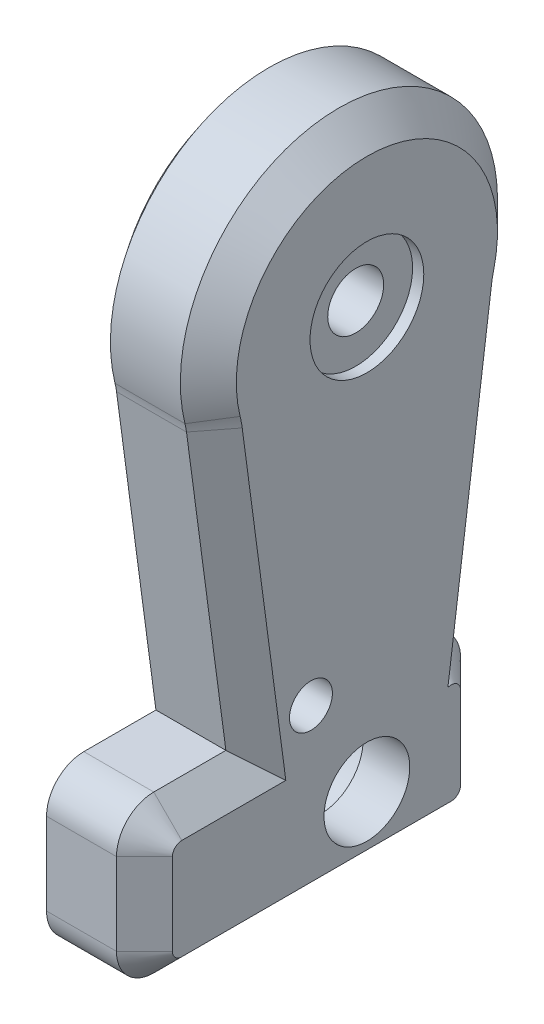
SolidWorks part; units mm, degrees
ref_plane "Front Plane" through (0, 0, 0) normal (0, 0, 1) x (1, 0, 0)
ref_plane "Top Plane" through (0, 0, 0) normal (0, 1, 0) x (1, 0, 0)
ref_plane "Right Plane" through (0, 0, 0) normal (1, 0, 0) x (0, 0, -1)
sketch "Sketch1" plane through (0, 0, 0) normal (1, 0, 0) x (0, 0, -1)
  line L0 (68.3427, -24.9297) -> (63.9535, -57.8487)
  line L1 (65.05, -60.6) -> (65.05, -69.4)
  line L2 (61.05, -73.4) -> (32.15, -73.4)
  line L3 (28.15, -69.4) -> (28.15, -60.6)
  line L4 (32.15, -56.6) -> (39.88, -56.6)
  line L5 (39.88, -56.6) -> (35.6573, -24.9297)
  arc A0 (35.4947, -24.0712) -> (68.5053, -24.0712) centre (52, -20) cw
  arc A1 (68.5053, -24.0712) -> (68.3427, -24.9297) centre (76.2725, -25.987) ccw
  arc A2 (63.9535, -57.8487) -> (65.05, -60.6) centre (61.05, -60.6) cw
  arc A3 (65.05, -69.4) -> (61.05, -73.4) centre (61.05, -69.4) cw
  arc A4 (32.15, -73.4) -> (28.15, -69.4) centre (32.15, -69.4) cw
  arc A5 (28.15, -60.6) -> (32.15, -56.6) centre (32.15, -60.6) cw
  arc A6 (35.6573, -24.9297) -> (35.4947, -24.0712) centre (27.7275, -25.987) ccw
extrude "Boss-Extrude1" add sketch "Sketch1" along normal blind 10.5 from offset 65.9
sketch "Sketch2" plane through (0, 0, 0) normal (1, 0, 0) x (0, 0, -1)
  line L0 (67.5497, -24.824) -> (63.1065, -58.1483)
  line L1 (64.25, -60.6) -> (64.25, -69.4)
  line L2 (61.05, -72.6) -> (32.15, -72.6)
  line L3 (28.95, -69.4) -> (28.95, -60.6)
  line L4 (32.15, -57.4) -> (40.7937, -57.4)
  line L5 (40.7937, -57.4) -> (36.4503, -24.824)
  arc A0 (36.2714, -23.8796) -> (67.7286, -23.8796) centre (52, -20) cw
  arc A1 (67.7286, -23.8796) -> (67.5497, -24.824) centre (76.2725, -25.987) ccw
  arc A2 (63.1065, -58.1483) -> (64.25, -60.6) centre (61.05, -60.6) cw
  arc A3 (64.25, -69.4) -> (61.05, -72.6) centre (61.05, -69.4) cw
  arc A4 (32.15, -72.6) -> (28.95, -69.4) centre (32.15, -69.4) cw
  arc A5 (28.95, -60.6) -> (32.15, -57.4) centre (32.15, -60.6) cw
  arc A6 (36.4503, -24.824) -> (36.2714, -23.8796) centre (27.7275, -25.987) ccw
extrude "Boss-Extrude2" add sketch "Sketch2" along normal blind 0.6 from offset 65.8 separate body
combine bodies "Combine1" operation type subtract main body 101 bodies to subtract 102
chamfer "Chamfer1" distance 3 angle 45 5 edges at (76.4, -41.3892, -66.1481) (76.4, -40.7649, -37.7686) (76.4, -24.4982, -68.4123) (76.4, -24.4982, -35.5877) (76.4, -3, -52)
chamfer "Chamfer2" distance 3 angle 45 8 edges at (76.4, -56.6, -37.5283) (76.4, -57.7716, -29.3216) (76.4, -57.787, -63.8937) (76.4, -65, -28.15) (76.4, -65, -65.05) (76.4, -72.2284, -29.3216) (76.4, -72.2284, -63.8784) (76.4, -73.4, -46.6)
sketch "Sketch3" plane through (0, 0, 0) normal (0, 0, 1) x (1, 0, 0)
  line L1 (65.9, -31.5) -> (68.2, -31.5)
  line L2 (65.9, -31.5) -> (65.9, -8.5)
  line L3 (65.9, -8.5) -> (68.2, -8.5)
  line L4 (68.2, -31.5) -> (68.2, -8.5)
extrude "Boss-Extrude3" add sketch "Sketch3" along normal blind 6.6 from offset 55.3 separate body offset against normal yes
combine bodies "Combine2" operation type subtract main body 103 bodies to subtract 104
sketch "Sketch4" plane through (0, 0, 0) normal (0, 0, 1) x (1, 0, 0)
  line L1 (65.9, -23.3) -> (68.2, -23.3)
  line L2 (65.9, -23.3) -> (65.9, -16.7)
  line L3 (65.9, -16.7) -> (68.2, -16.7)
  line L4 (68.2, -23.3) -> (68.2, -16.7)
extrude "Boss-Extrude4" add sketch "Sketch4" along normal blind 23 from offset 63.5 separate body offset against normal yes
combine bodies "Combine3" operation type subtract main body 105 bodies to subtract 106
sketch "Sketch5" plane through (0, 0, 0) normal (1, 0, 0) x (0, 0, -1)
  circle A0 centre (52, -20) radius 4.6
extrude "Boss-Extrude5" add sketch "Sketch5" along normal blind 2.3 from offset 65.9 separate body
combine bodies "Combine4" operation type subtract main body 107 bodies to subtract 108
sketch "Sketch6" plane through (0, 0, 0) normal (1, 0, 0) x (0, 0, -1)
  circle A0 centre (52, -20) radius 6.1
extrude "Boss-Extrude6" add sketch "Sketch6" along normal blind 1.7 from offset 75.2 separate body
combine bodies "Combine5" operation type subtract main body 109 bodies to subtract 110
sketch "Sketch7" plane through (0, 0, 0) normal (1, 0, 0) x (0, 0, -1)
  circle A0 centre (52, -20) radius 3
extrude "Boss-Extrude7" add sketch "Sketch7" along normal blind 7.2 from offset 68.1 separate body
combine bodies "Combine6" operation type subtract main body 111 bodies to subtract 112
sketch "Sketch8" plane through (0, 0, 0) normal (0, 0, 1) x (1, 0, 0)
  line L1 (68.1, -14.5) -> (74.2, -14.5)
  line L2 (68.1, -14.5) -> (68.1, -13.4)
  line L3 (68.1, -13.4) -> (74.2, -13.4)
  line L4 (74.2, -14.5) -> (74.2, -13.4)
extrude "Boss-Extrude8" add sketch "Sketch8" along normal blind 1.8 from offset 52.9 separate body offset against normal yes
combine bodies "Combine7" operation type subtract main body 113 bodies to subtract 114
sketch "Sketch9" plane through (0, 0, 0) normal (0, 0, 1) x (1, 0, 0)
  line L1 (68.1, -20.9) -> (74.2, -20.9)
  line L2 (68.1, -20.9) -> (68.1, -19.1)
  line L3 (68.1, -19.1) -> (74.2, -19.1)
  line L4 (74.2, -20.9) -> (74.2, -19.1)
extrude "Boss-Extrude9" add sketch "Sketch9" along normal blind 1.1 from offset 46.5 separate body offset against normal yes
combine bodies "Combine8" operation type subtract main body 115 bodies to subtract 116
sketch "Sketch10" plane through (0, 0, 0) normal (0, 0, 1) x (1, 0, 0)
  line L1 (68.1, -26.6) -> (74.2, -26.6)
  line L2 (68.1, -26.6) -> (68.1, -25.5)
  line L3 (68.1, -25.5) -> (74.2, -25.5)
  line L4 (74.2, -26.6) -> (74.2, -25.5)
extrude "Boss-Extrude10" add sketch "Sketch10" along normal blind 1.8 from offset 52.9 separate body offset against normal yes
combine bodies "Combine9" operation type subtract main body 117 bodies to subtract 118
sketch "Sketch11" plane through (0, 0, 0) normal (0, 0, 1) x (1, 0, 0)
  line L1 (68.1, -20.9) -> (74.2, -20.9)
  line L2 (68.1, -20.9) -> (68.1, -19.1)
  line L3 (68.1, -19.1) -> (74.2, -19.1)
  line L4 (74.2, -20.9) -> (74.2, -19.1)
extrude "Boss-Extrude11" add sketch "Sketch11" along normal blind 1.1 from offset 58.6 separate body offset against normal yes
combine bodies "Combine10" operation type subtract main body 119 bodies to subtract 120
sketch "Sketch12" plane through (0, 0, 0) normal (0, 0, 1) x (1, 0, 0)
  line L1 (68.1, -13.4) -> (75.4, -13.4)
  line L2 (68.1, -13.4) -> (68.1, -10)
  line L3 (68.1, -10) -> (75.4, -10)
  line L4 (75.4, -13.4) -> (75.4, -10)
extrude "Boss-Extrude12" add sketch "Sketch12" along normal blind 1.8 from offset 52.9 separate body offset against normal yes
combine bodies "Combine11" operation type subtract main body 121 bodies to subtract 122
sketch "Sketch13" plane through (0, 0, 0) normal (0, 0, 1) x (1, 0, 0)
  line L1 (68.1, -20.9) -> (75.4, -20.9)
  line L2 (68.1, -20.9) -> (68.1, -19.1)
  line L3 (68.1, -19.1) -> (75.4, -19.1)
  line L4 (75.4, -20.9) -> (75.4, -19.1)
extrude "Boss-Extrude13" add sketch "Sketch13" along normal blind 3.4 from offset 45.4 separate body offset against normal yes
combine bodies "Combine12" operation type subtract main body 123 bodies to subtract 124
sketch "Sketch14" plane through (0, 0, 0) normal (0, 0, 1) x (1, 0, 0)
  line L1 (68.1, -30) -> (75.4, -30)
  line L2 (68.1, -30) -> (68.1, -26.6)
  line L3 (68.1, -26.6) -> (75.4, -26.6)
  line L4 (75.4, -30) -> (75.4, -26.6)
extrude "Boss-Extrude14" add sketch "Sketch14" along normal blind 1.8 from offset 52.9 separate body offset against normal yes
combine bodies "Combine13" operation type subtract main body 125 bodies to subtract 126
sketch "Sketch15" plane through (0, 0, 0) normal (0, 0, 1) x (1, 0, 0)
  line L1 (68.1, -20.9) -> (75.4, -20.9)
  line L2 (68.1, -20.9) -> (68.1, -19.1)
  line L3 (68.1, -19.1) -> (75.4, -19.1)
  line L4 (75.4, -20.9) -> (75.4, -19.1)
extrude "Boss-Extrude15" add sketch "Sketch15" along normal blind 3.4 from offset 62 separate body offset against normal yes
combine bodies "Combine14" operation type subtract main body 127 bodies to subtract 128
sketch "Sketch16" plane through (0, 0, 0) normal (1, 0, 0) x (0, 0, -1)
  line L0 (66.0954, -14.8697) -> (65.5316, -15.0749)
  line L1 (38.4684, -15.0749) -> (37.9046, -14.8697)
  arc A0 (37.9046, -14.8697) -> (66.0954, -14.8697) centre (52, -20) cw
  arc A1 (65.5316, -15.0749) -> (38.4684, -15.0749) centre (52, -20) ccw
extrude "Boss-Extrude16" add sketch "Sketch16" along normal blind 2.05 from offset 64.4
sketch "Sketch17" plane through (0, 0, 0) normal (0, 0, 1) x (1, 0, 0)
  line L1 (66.3, -66) -> (70.4, -66)
  line L2 (66.3, -66) -> (66.3, -64)
  line L3 (66.3, -64) -> (70.4, -64)
  line L4 (70.4, -66) -> (70.4, -64)
extrude "Boss-Extrude17" add sketch "Sketch17" along normal blind 2.9 from offset 62.125 separate body offset against normal yes
combine bodies "Combine15" operation type subtract main body 130 bodies to subtract 131
sketch "Sketch18" plane through (0, 0, 0) normal (0, 0, 1) x (1, 0, 0)
  line L1 (66.3, -66) -> (70.4, -66)
  line L2 (66.3, -66) -> (66.3, -64)
  line L3 (66.3, -64) -> (70.4, -64)
  line L4 (70.4, -66) -> (70.4, -64)
extrude "Boss-Extrude18" add sketch "Sketch18" along normal blind 2.9 from offset 33.975 separate body offset against normal yes
combine bodies "Combine16" operation type subtract main body 132 bodies to subtract 133
sketch "Sketch19" plane through (0, 0, 0) normal (0, 0, 1) x (1, 0, 0)
  line L1 (66.3, -71.5) -> (68.4, -71.5)
  line L2 (66.3, -71.5) -> (66.3, -58.5)
  line L3 (66.3, -58.5) -> (68.4, -58.5)
  line L4 (68.4, -71.5) -> (68.4, -58.5)
extrude "Boss-Extrude19" add sketch "Sketch19" along normal blind 23.4 from offset 58.3 separate body offset against normal yes
combine bodies "Combine17" operation type subtract main body 134 bodies to subtract 135
sketch "Sketch20" plane through (0, 0, 0) normal (1, 0, 0) x (0, 0, -1)
  circle A0 centre (52, -65) radius 6.7
extrude "Boss-Extrude20" add sketch "Sketch20" along normal blind 5.1 from offset 66.3 separate body
combine bodies "Combine18" operation type subtract main body 136 bodies to subtract 137
sketch "Sketch21" plane through (0, 0, 0) normal (1, 0, 0) x (0, 0, -1)
  circle A0 centre (52, -65) radius 4.6
extrude "Boss-Extrude21" add sketch "Sketch21" along normal blind 5.8 from offset 71.1 separate body
combine bodies "Combine19" operation type subtract main body 138 bodies to subtract 139
sketch "Sketch22" plane through (0, 0, 0) normal (0, 0, 1) x (1, 0, 0)
  line L1 (66.3, -57.8) -> (74.6, -57.8)
  line L2 (66.3, -57.8) -> (66.3, -37)
  line L3 (66.3, -37) -> (74.6, -37)
  line L4 (74.6, -57.8) -> (74.6, -37)
extrude "Boss-Extrude22" add sketch "Sketch22" along normal blind 6 from offset 55 separate body offset against normal yes
combine bodies "Combine20" operation type subtract main body 140 bodies to subtract 141
sketch "Sketch23" plane through (0, 0, 0) normal (1, 0, 0) x (0, 0, -1)
  circle A0 centre (46, -54) radius 2.3
extrude "Boss-Extrude23" add sketch "Sketch23" along normal blind 6 from offset 70.9 separate body
combine bodies "Combine21" operation type subtract main body 142 bodies to subtract 143
sketch "Sketch24" plane through (0, 0, 0) normal (1, 0, 0) x (0, 0, -1)
  circle A0 centre (46, -54) radius 1.3
extrude "Boss-Extrude24" add sketch "Sketch24" along normal blind 4.65 from offset 66.3 separate body
combine bodies "Combine22" operation type subtract main body 144 bodies to subtract 145
sketch "Sketch25" plane through (0, 0, 0) normal (0, 0, 1) x (1, 0, 0)
  line L1 (66.3, -48.05) -> (70.4, -48.05)
  line L2 (66.3, -48.05) -> (66.3, -43.95)
  line L3 (66.3, -43.95) -> (70.4, -43.95)
  line L4 (70.4, -48.05) -> (70.4, -43.95)
extrude "Boss-Extrude25" add sketch "Sketch25" along normal blind 2.2 from offset 60.6 separate body offset against normal yes
combine bodies "Combine23" operation type subtract main body 146 bodies to subtract 147
sketch "Sketch26" plane through (0, 0, 0) normal (0, 1, 0) x (1, 0, 0)
  line L0 (70.6, 59) -> (70.6, 60)
  line L1 (70.6, 60) -> (64.4, 60)
  line L2 (64.4, 60) -> (64.4, 60.4)
  line L3 (64.4, 60.4) -> (63.8, 60.4)
  line L4 (63.8, 60.4) -> (63, 59.6)
  line L5 (63, 59.6) -> (63, 59)
  line L6 (63, 59) -> (70.6, 59)
extrude "Boss-Extrude26" add sketch "Sketch26" along normal blind 3.5 from offset 47.75 offset against normal yes
sketch "Sketch27" plane through (0, 0, 0) normal (0, 0, 1) x (1, 0, 0)
  line L1 (66.3, -48.05) -> (70.4, -48.05)
  line L2 (66.3, -48.05) -> (66.3, -43.95)
  line L3 (66.3, -43.95) -> (70.4, -43.95)
  line L4 (70.4, -48.05) -> (70.4, -43.95)
extrude "Boss-Extrude27" add sketch "Sketch27" along normal blind 2.2 from offset 45.6 separate body offset against normal yes
combine bodies "Combine24" operation type subtract main body 149 bodies to subtract 150
sketch "Sketch28" plane through (0, 0, 0) normal (0, 1, 0) x (1, 0, 0)
  line L0 (70.6, 45) -> (70.6, 44)
  line L1 (70.6, 44) -> (64.4, 44)
  line L2 (64.4, 44) -> (64.4, 43.6)
  line L3 (64.4, 43.6) -> (63.8, 43.6)
  line L4 (63.8, 43.6) -> (63, 44.4)
  line L5 (63, 44.4) -> (63, 45)
  line L6 (63, 45) -> (70.6, 45)
extrude "Boss-Extrude28" add sketch "Sketch28" along normal blind 3.5 from offset 47.75 offset against normal yes
